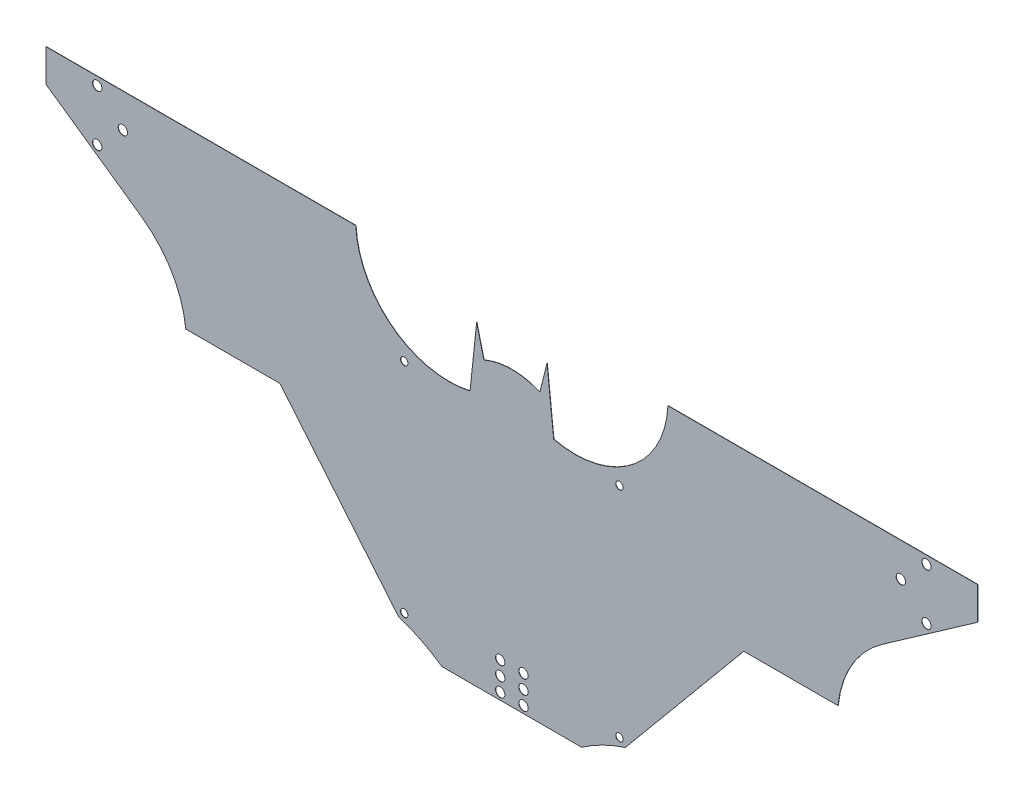
SolidWorks part; units mm, degrees
ref_plane "Front Plane" through (0, 0, 0) normal (0, 0, 1) x (1, 0, 0)
ref_plane "Top Plane" through (0, 0, 0) normal (0, 1, 0) x (1, 0, 0)
ref_plane "Right Plane" through (0, 0, 0) normal (1, 0, 0) x (0, 0, -1)
sketch "Sketch1" plane through (0, 0, 0) normal (0, 0, 1) x (1, 0, 0)
  line L0 (0, 145.9429) -> (0, -145.9429) construction
  line L1 (67, 50) -> (220, 50)
  line L2 (-67, 50) -> (-220, 50)
  line L3 (17.9555, 13) -> (15.1177, 40)
  line L4 (15.1177, 40) -> (12, 27.4955)
  line L5 (-15.1177, 40) -> (-12, 27.4955)
  line L6 (-17.9555, 13) -> (-15.1177, 40)
  line L7 (220, 50) -> (158.9525, 7.2541)
  line L8 (-220, 50) -> (-158.9525, 7.2541)
  line L9 (-140, -25) -> (-99.5632, -25)
  line L10 (140, -25) -> (99.5632, -25)
  arc A0 (67, 50) -> (17.9555, 13) centre (27.0477, 51.953) cw
  arc A1 (-67, 50) -> (-17.9555, 13) centre (-27.0477, 51.953) ccw
  arc A2 (12, 27.4955) -> (-12, 27.4955) centre (0, 0) ccw
  arc A3 (158.9525, 7.2541) -> (140, -25) centre (184.7635, -29.6077) ccw
  arc A4 (-99.5632, -25) -> (0, -115.6638) centre (-99.5632, -125) cw
  arc A5 (99.5632, -25) -> (0, -115.6638) centre (99.5632, -125) ccw
  arc A6 (-158.9525, 7.2541) -> (-140, -25) centre (-184.7635, -29.6077) cw
  dimension "D2" = 40
  dimension "D5" = 30
  dimension "D10" = 220
  dimension "D12" = 45
  dimension "D13" = 100
  dimension "D1" = 134
  dimension "D3" = 84
  dimension "D4" = 160
  dimension "D6" = 50
  dimension "D7" = 24
  dimension "D8" = 37
  dimension "D9" = 10
  dimension "D11" = 35
  dimension "D14" = 140
  dimension "D15" = 75
  dimension "D16" = 140
  dimension "D17" = 99.5632
sketch "Sketch2" plane through (0, 0, 0) normal (0, 0, 1) x (1, 0, 0)
  line L0 (0, 145.9429) -> (0, -145.9429) construction
  line L7 (0, 0) -> (0, -152.8683) construction
  line L8 (99.5632, -21.9265) -> (48.69, -83.15)
  line L9 (-99.5632, -21.9265) -> (-48.69, -83.15)
  line L26 (158.9525, 10.3276) -> (220, 53.0735)
  line L27 (220, 53.0735) -> (67, 53.0735)
  line L28 (17.9555, 16.0735) -> (15.1177, 43.0735)
  line L29 (15.1177, 43.0735) -> (12, 30.569)
  line L30 (-12, 30.569) -> (-15.1177, 43.0735)
  line L31 (-15.1177, 43.0735) -> (-17.9555, 16.0735)
  line L32 (-67, 53.0735) -> (-220, 53.0735)
  line L33 (-220, 53.0735) -> (-158.9525, 10.3276)
  line L34 (-140, -21.9265) -> (-99.5632, -21.9265)
  line L35 (99.5632, -21.9265) -> (140, -21.9265)
  circle A2 centre (46.19, 13) radius 1.5875
  circle A3 centre (-46.19, 13) radius 1.5875
  circle A4 centre (46.19, -80.65) radius 1.5875
  circle A5 centre (-46.19, -80.65) radius 1.5875
  arc A6 (48.69, -83.15) -> (0, -150) centre (70.2366, -150) ccw
  arc A7 (-48.69, -83.15) -> (0, -150) centre (-70.2366, -150) cw
  arc A14 (17.9555, 16.0735) -> (67, 53.0735) centre (27.0477, 55.0265) ccw
  arc A15 (12, 30.569) -> (-12, 30.569) centre (0, 3.0735) ccw
  arc A16 (-67, 53.0735) -> (-17.9555, 16.0735) centre (-27.0477, 55.0265) ccw
  arc A17 (-140, -21.9265) -> (-158.9525, 10.3276) centre (-184.7635, -26.5342) ccw
  arc A20 (158.9525, 10.3276) -> (140, -21.9265) centre (184.7635, -26.5342) ccw
  point P0 (0, 40)
  dimension "D3" = 93.65
  dimension "D4" = 3.175
  dimension "D5" = 3.175
  dimension "D6" = 3.175
  dimension "D7" = 3.175
  dimension "D2" = 40
  dimension "D9" = 25
  dimension "D10" = 46.19
  dimension "D11" = 27
  dimension "D12" = 46.19
  dimension "D13" = 99.5632
  dimension "D14" = 2.5
  dimension "D15" = 2.5
  dimension "D16" = 150
extrude "Boss-Extrude1" add sketch "Sketch2" along normal blind 0.118
sketch "Sketch3" plane through (0, 0, 0) normal (0, 0, -1) x (-1, 0, 0)
  line L0 (0, -121.719) -> (0, 0) construction
  line L1 (178, 49.5735) -> (178, 27.5735) construction
  line L2 (178, 27.5735) -> (178, 49.5735) construction
  line L3 (67, 53.0735) -> (220, 53.0735) construction
  circle A0 centre (178, 49.5735) radius 2
  circle A1 centre (178, 27.5735) radius 2
  circle A2 centre (167, 38.5735) radius 2
  point P7 (165, 44.5361)
  point P8 (150, 29.1207)
  point P11 (165, 46.045)
  dimension "D1" = 4
  dimension "D2" = 4
  dimension "D5" = 4
  dimension "D3" = 22
  dimension "D4" = 42
  dimension "D6" = 11
  dimension "D7" = 11
  dimension "D8" = 3.5
extrude "Cut-Extrude1" cut sketch "Sketch3" against normal through all
mirror "Mirror2" about plane through (0, 0, 0) normal (1, 0, 0) of "Cut-Extrude1"
chamfer "Chamfer1" distance 20 angle 90 2 edges at (-220, 53.0735, 0.059) (220, 53.0735, 0.059) first distance on face at (-143.5, 53.0735, 0.059) first distance on face at (143.5, 53.0735, 0.059)
sketch "Sketch4" plane through (0, 0, 0) normal (0, 0, -1) x (-1, 0, 0)
  line L5 (-30, -207.569) -> (30, -207.569)
  line L6 (-30, -207.569) -> (-30, -92.431)
  line L7 (-30, -92.431) -> (30, -92.431)
  line L8 (30, -207.569) -> (30, -92.431)
  line L9 (-30, -207.569) -> (30, -92.431) construction
  line L10 (-30, -92.431) -> (30, -207.569) construction
  arc A0 (48.69, -83.15) -> (0, -150) centre (70.2366, -150) ccw construction
  point P0 (0, -150)
  dimension "D1" = 60
extrude "Cut-Extrude2" cut sketch "Sketch4" against normal through all
sketch "Sketch5" plane through (0, 0, 0) normal (0, 0, -1) x (-1, 0, 0)
  line L0 (0, 0) -> (0, -92.431) construction
  line L1 (30, -92.431) -> (-30, -92.431) construction
  circle A0 centre (-5, -89.431) radius 2
  circle A1 centre (5, -89.431) radius 2
  dimension "D1" = 4
  dimension "D2" = 5
  dimension "D3" = 3
  dimension "D4" = 2
extrude "Cut-Extrude3" cut sketch "Sketch5" against normal through all contours A0 | A1
pattern_linear "LPattern1" count 3 spacing 6 along (0, 1, 0) of "Cut-Extrude3"
